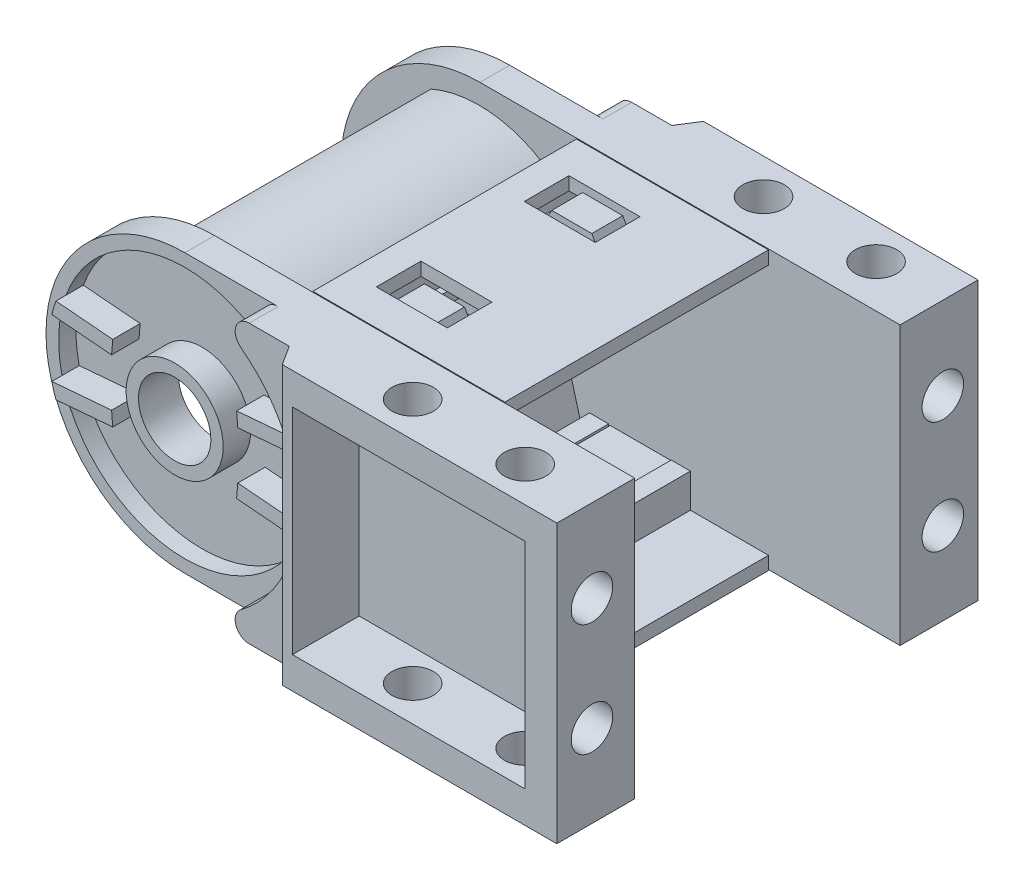
SolidWorks part; units mm, degrees
material "ABS"
ref_plane "Front Plane" through (0, 0, 0) normal (0, 0, 1) x (1, 0, 0)
ref_plane "Top Plane" through (0, 0, 0) normal (0, 1, 0) x (1, 0, 0)
ref_plane "Right Plane" through (0, 0, 0) normal (1, 0, 0) x (0, 0, -1)
sketch "Sketch1" plane through (0, 0, 0) normal (0, 0, 1) x (1, 0, 0)
  line L0 (0, 19.75) -> (59.75, 19.75)
  line L1 (59.75, 19.75) -> (59.75, -19.75)
  line L2 (59.75, -19.75) -> (0, -19.75)
  arc A0 (0, 19.75) -> (0, -19.75) centre (0, 0) ccw
  point P1 (-19.75, 0)
  dimension "D1" = 39.5
  dimension "D2" = 79.5
extrude "Boss-Extrude1" add sketch "Sketch1" against normal blind 11.08 from offset 29.95
sketch "Sketch2" plane through (0, 0, 29.95) normal (0, 0, 1) x (1, 0, 0)
  line L0 (59.75, -19.75) -> (59.75, 19.75) construction
  line L1 (22.15, 15.25) -> (55.25, 15.25)
  line L2 (22.15, 15.25) -> (22.15, -15.25)
  line L3 (22.15, -15.25) -> (55.25, -15.25)
  line L4 (55.25, 15.25) -> (55.25, -15.25)
  line L5 (38.7, -15.25) -> (38.7, 15.25) construction
  line L6 (22.15, 0) -> (55.25, 0) construction
  line L7 (59.75, 19.75) -> (0, 19.75) construction
  point P0 (38.7, 0)
  dimension "D1" = 4.5
  dimension "D2" = 4.5
  dimension "D3" = 33.1
extrude "Cut-Extrude1" cut sketch "Sketch2" against normal blind 9.5
sketch "Sketch3" plane through (0, 0, 29.95) normal (0, 0, 1) x (1, 0, 0)
  line L0 (0, -19.75) -> (59.75, -19.75) construction
  line L1 (59.75, 19.75) -> (0, 19.75) construction
  line L2 (0, -19.75) -> (18.95, -19.75)
  line L3 (18.95, 19.75) -> (0, 19.75)
  line L4 (18.95, 19.75) -> (18.95, -19.75)
  line L5 (59.75, -19.75) -> (59.75, 19.75) construction
  arc A0 (0, 19.75) -> (0, -19.75) centre (0, 0) ccw construction
  arc A1 (0, 19.75) -> (0, -19.75) centre (0, 0) ccw
  point P7 (-19.75, 0)
  dimension "D1" = 40.8
extrude "Cut-Extrude2" cut sketch "Sketch3" against normal blind 2.75
chamfer "Chamfer1" distance 1.75 distance2 2.75 1 edges at (18.95, 0, 29.95) first distance on face at (39.35, 0, 29.95)
sketch "Sketch20" plane through (0, 0, 27.2) normal (0, 0, 1) x (1, 0, 0)
  circle A0 centre (0, 0) radius 20.15
  dimension "D1" = 40.3
extrude "Cut-Extrude10" cut sketch "Sketch20" against normal blind 4.1
fillet "Fillet3" radius 2 2 edges at (3.995, -19.75, 25.15) (3.995, 19.75, 25.15)
sketch "Sketch21" plane through (0, 0, 23.1) normal (0, 0, 1) x (1, 0, 0)
  circle A0 centre (0, 0) radius 17.95
  dimension "D1" = 35.9
extrude "Cut-Extrude11" cut sketch "Sketch21" against normal offset from surface (2.45 mm away) 6.55 up to face at (15.6464, 15.8587, 27.2)
sketch "Sketch22" plane through (0, 0, 20.65) normal (0, 0, 1) x (1, 0, 0)
  circle A0 centre (0, 0) radius 5.15
  dimension "D1" = 10.3
extrude "Cut-Extrude12" cut sketch "Sketch22" against normal through all
sketch "Sketch23" plane through (0, 0, 20.65) normal (0, 0, 1) x (1, 0, 0)
  line L0 (17.2108, 5.0982) -> (8.8897, 4.4035) construction
  line L1 (-17.95, 0) -> (17.95, 0) construction
  line L2 (16.8907, 6.075) -> (8.8065, 5.4)
  line L3 (17.4716, 4.1165) -> (8.9729, 3.4069)
  line L4 (8.8065, 5.4) -> (8.9729, 3.4069)
  line L5 (17.1276, 6.0948) -> (8.8065, 5.4) construction
  line L6 (17.4716, -4.1165) -> (8.9729, -3.4069)
  line L7 (8.8065, -5.4) -> (8.9729, -3.4069)
  line L8 (16.8907, -6.075) -> (8.8065, -5.4)
  line L9 (17.294, 4.1017) -> (8.9729, 3.4069) construction
  line L10 (0, 0) -> (0, -5.15) construction
  line L11 (-8.8065, -5.4) -> (-8.9729, -3.4069)
  line L12 (-16.8907, -6.075) -> (-8.8065, -5.4)
  line L13 (-17.4716, -4.1165) -> (-8.9729, -3.4069)
  line L14 (-17.4716, 4.1165) -> (-8.9729, 3.4069)
  line L15 (-8.8065, 5.4) -> (-8.9729, 3.4069)
  line L16 (-16.8907, 6.075) -> (-8.8065, 5.4)
  circle A0 centre (0, 0) radius 5.15 construction
  circle A1 centre (0, 0) radius 5.15
  circle A2 centre (0, 0) radius 6.9
  circle A3 centre (0, 0) radius 17.95 construction
  arc A5 (17.4716, 4.1165) -> (16.8907, 6.075) centre (0, 0) ccw
  arc A6 (17.4716, -4.1165) -> (16.8907, -6.075) centre (0, 0) cw
  arc A7 (-17.4716, -4.1165) -> (-16.8907, -6.075) centre (0, 0) ccw
  arc A8 (-17.4716, 4.1165) -> (-16.8907, 6.075) centre (0, 0) cw
  point P12 (0, 0)
  dimension "D1" = 13.8
  dimension "D4" = 8.35
  dimension "D5" = 10.8
  dimension "D6" = 12.15
  dimension "D2" = 1
  dimension "D3" = 1
extrude "Boss-Extrude11" add sketch "Sketch23" along normal blind 3.9
sketch "Sketch6" plane through (0, 19.75, 0) normal (0, 1, 0) x (1, 0, 0)
  line L0 (59.75, -24.95) -> (20.7, -24.95) construction
  line L1 (59.75, -18.87) -> (59.75, -29.95) construction
  line L3 (59.75, -29.95) -> (20.7, -29.95) construction
  circle A0 centre (50.25, -24.95) radius 2.95
  circle A1 centre (34.25, -24.95) radius 2.95
  dimension "D1" = 5.9
  dimension "D2" = 16
  dimension "D3" = 9.5
  dimension "D4" = 5
extrude "Cut-Extrude4" cut sketch "Sketch6" against normal through all
sketch "Sketch7" plane through (59.75, 0, 0) normal (1, 0, 0) x (0, 0, -1)
  line L0 (-24.95, 19.75) -> (-24.95, -19.75) construction
  line L1 (-18.87, 19.75) -> (-29.95, 19.75) construction
  line L2 (-18.87, -19.75) -> (-29.95, -19.75) construction
  line L3 (-24.95, 0) -> (-18.87, 0) construction
  line L4 (-18.87, -19.75) -> (-18.87, 19.75) construction
  line L5 (-29.95, -19.75) -> (-29.95, 19.75) construction
  circle A0 centre (-24.95, 8) radius 2.95
  circle A1 centre (-24.95, -8) radius 2.95
  dimension "D1" = 16
  dimension "D2" = 5.9
  dimension "D3" = 5
extrude "Cut-Extrude5" cut sketch "Sketch7" against normal up to next
sketch "Sketch12" plane through (0, 0, 18.87) normal (0, 0, -1) x (-1, 0, 0)
  line L0 (-27.425, 17.15) -> (-18.325, 17.15)
  line L1 (-22.875, 17.15) -> (-22.875, 13.25) construction
  line L2 (-27.425, 17.15) -> (-28.25, 15.65)
  line L3 (-28.25, 14.85) -> (-27.225, 14.85)
  line L4 (-27.225, 14.85) -> (-27.225, 13.25)
  line L5 (-18.525, 14.85) -> (-18.525, 13.25)
  line L6 (-17.5, 14.85) -> (-18.525, 14.85)
  line L7 (-18.325, 17.15) -> (-17.5, 15.65)
  line L8 (-18.525, 13.25) -> (-27.225, 13.25)
  line L9 (-28.25, 15.65) -> (-28.25, 14.85)
  line L10 (0, 0) -> (-59.75, 0) construction
  line L11 (-59.75, -19.75) -> (-59.75, 19.75) construction
  line L20 (-17.5, 15.65) -> (-17.5, 14.85)
  line L21 (-22.875, -17.15) -> (-22.875, -13.25) construction
  line L22 (-17.5, -15.65) -> (-17.5, -14.85)
  line L23 (-28.25, -15.65) -> (-28.25, -14.85)
  line L24 (-18.525, -13.25) -> (-27.225, -13.25)
  line L25 (-18.325, -17.15) -> (-17.5, -15.65)
  line L26 (-17.5, -14.85) -> (-18.525, -14.85)
  line L27 (-18.525, -14.85) -> (-18.525, -13.25)
  line L28 (-27.225, -14.85) -> (-27.225, -13.25)
  line L29 (-28.25, -14.85) -> (-27.225, -14.85)
  line L30 (-27.425, -17.15) -> (-28.25, -15.65)
  line L31 (-27.425, -17.15) -> (-18.325, -17.15)
  point P3 (-22.875, 17.15)
  dimension "D1" = 10.75
  dimension "D2" = 31.5
  dimension "D3" = 26.5
  dimension "D4" = 34.3
  dimension "D5" = 8.7
  dimension "D6" = 2.3
  dimension "D7" = 0.8
  dimension "D8" = 9.1
extrude "Boss-Extrude4" add sketch "Sketch12" along normal offset from surface (10.92 mm away) 22 up to face at (40.225, 0, 29.95)
sketch "Sketch13" plane through (0, 0, 7.95) normal (0, 0, -1) x (-1, 0, 0)
  line L0 (-26.7, 17.15) -> (-25.725, 18.9)
  line L1 (-18.325, 17.15) -> (-27.425, 17.15) construction
  line L2 (-25.725, 18.9) -> (-20.025, 18.9)
  line L3 (-20.025, 18.9) -> (-19.05, 17.15)
  line L4 (-26.7, 17.15) -> (-19.05, 17.15)
  line L5 (-22.875, 18.9) -> (-22.875, 17.15) construction
  line L6 (0, 0) -> (-59.75, 0) construction
  line L7 (-59.75, -19.75) -> (-59.75, 19.75) construction
  line L8 (-20.025, -18.9) -> (-19.05, -17.15)
  line L9 (-26.7, -17.15) -> (-19.05, -17.15)
  line L10 (-26.7, -17.15) -> (-25.725, -18.9)
  line L11 (-25.725, -18.9) -> (-20.025, -18.9)
  point P8 (-22.875, 17.15)
  dimension "D1" = 7.65
  dimension "D2" = 5.7
  dimension "D3" = 1.75
extrude "Boss-Extrude5" add sketch "Sketch13" against normal blind 4.4 from offset 1.1 offset against normal yes
sketch "Sketch14" plane through (0, 0, 0) normal (0, 0, 1) x (1, 0, 0)
  line L0 (41.15, 19.75) -> (13.85, 19.75)
  line L1 (59.75, 19.75) -> (0, 19.75) construction
  line L2 (13.85, 19.75) -> (11.7872, 12.25)
  line L3 (59.75, -19.75) -> (59.75, 19.75) construction
  line L4 (41.15, 17.87) -> (30.05, 17.87)
  line L5 (15.2827, 17.87) -> (12.6469, 8.2867)
  line L6 (-6.85, 15.5588) -> (-6.0925, 13.8382)
  line L7 (41.15, 19.75) -> (41.15, 17.87)
  line L8 (30.05, 13.05) -> (30.05, 17.87)
  line L9 (27.325, 13.05) -> (30.05, 13.05)
  line L10 (27.325, 13.05) -> (27.325, 14.75)
  line L11 (27.325, 14.75) -> (28.35, 14.75)
  line L12 (28.35, 14.75) -> (28.35, 17.87)
  line L13 (28.35, 17.87) -> (17.4, 17.87)
  line L14 (41.15, 17.87) -> (15.2827, 17.87) construction
  line L15 (18.425, 13.05) -> (15.7, 13.05)
  line L16 (15.7, 13.05) -> (15.7, 17.87)
  line L17 (22.875, 13.25) -> (22.875, 19.75) construction
  line L18 (18.425, 13.25) -> (18.425, 14.75)
  line L19 (17.4, 14.75) -> (17.4, 15.65)
  line L20 (18.425, 14.75) -> (17.4, 14.75)
  line L21 (18.425, 13.05) -> (18.425, 14.75)
  line L22 (17.4, 14.75) -> (17.4, 17.87)
  line L23 (18.425, 14.75) -> (17.4, 14.75)
  line L24 (18.525, 13.25) -> (27.225, 13.25) construction
  line L25 (15.7, 17.87) -> (15.2827, 17.87)
  arc A0 (11.7872, 12.25) -> (-6.85, 15.5588) centre (0, 0) ccw
  arc A1 (12.6469, 8.2867) -> (-6.0925, 13.8382) centre (0, 0) ccw
  dimension "D1" = 17
  dimension "D2" = 48
  dimension "D3" = 27.3
  dimension "D4" = 7.5
  dimension "D5" = 18.6
  dimension "D7" = 0.1
  dimension "D6" = 1.88
  dimension "D8" = 1.7
extrude "Boss-Extrude6" add sketch "Sketch14" along normal mid plane 37.5 separate body
sketch "Sketch15" plane through (0, 19.75, 0) normal (0, 1, 0) x (1, 0, 0)
  line L1 (27.925, -7.35) -> (17.825, -7.35)
  line L2 (27.925, -7.35) -> (27.925, -13.7)
  line L5 (27.925, -13.7) -> (17.825, -13.7)
  line L6 (17.825, -7.35) -> (17.825, -13.7)
  line L7 (22.875, -13.7) -> (22.875, -7.35) construction
  line L8 (27.925, -10.525) -> (17.825, -10.525) construction
  line L9 (0, 0) -> (44.1536, 0) construction
  line L10 (17.825, 7.35) -> (17.825, 13.7)
  line L11 (27.925, 13.7) -> (17.825, 13.7)
  line L12 (27.925, 7.35) -> (27.925, 13.7)
  line L13 (27.925, 7.35) -> (17.825, 7.35)
  line L14 (19.05, -9.05) -> (26.7, -13.45) construction
  point P14 (22.875, -11.25)
  point P172 (22.875, -10.525)
  dimension "D1" = 10.1
  dimension "D2" = 14.7
  dimension "D3" = 27.4
extrude "Cut-Extrude9" cut sketch "Sketch15" against normal up to surface (5 mm away) up to face at (27.8375, 14.75, 0)
sketch "Sketch16" plane through (0, 13.05, 0) normal (0, -1, 0) x (1, 0, 0)
  line L0 (30.05, 18.75) -> (30.05, -18.75) construction
  line L1 (30.05, 1) -> (15.7, 1)
  line L2 (30.05, 1) -> (30.05, -1)
  line L3 (30.05, -1) -> (15.7, -1)
  line L4 (15.7, 1) -> (15.7, -1)
  line L5 (22.875, -1) -> (22.875, 1) construction
  line L6 (30.05, 0) -> (15.7, 0) construction
  line L7 (15.7, 18.75) -> (15.7, -18.75) construction
  point P10 (22.875, 0)
  point P11 (22.875, 15.8388)
  point P12 (38.1315, 0)
  point P212 (22.875, 0)
  dimension "D1" = 2
extrude "Boss-Extrude7" add sketch "Sketch16" against normal up to surface (4.82 mm away) up to face at (35.6, 17.87, 0)
mirror "Mirror1" about plane through (0, 0, 0) normal (0, 0, 1) of bodies 113 121
mirror "Mirror2" about plane through (0, 0, 0) normal (0, 1, 0) of bodies 118 115
